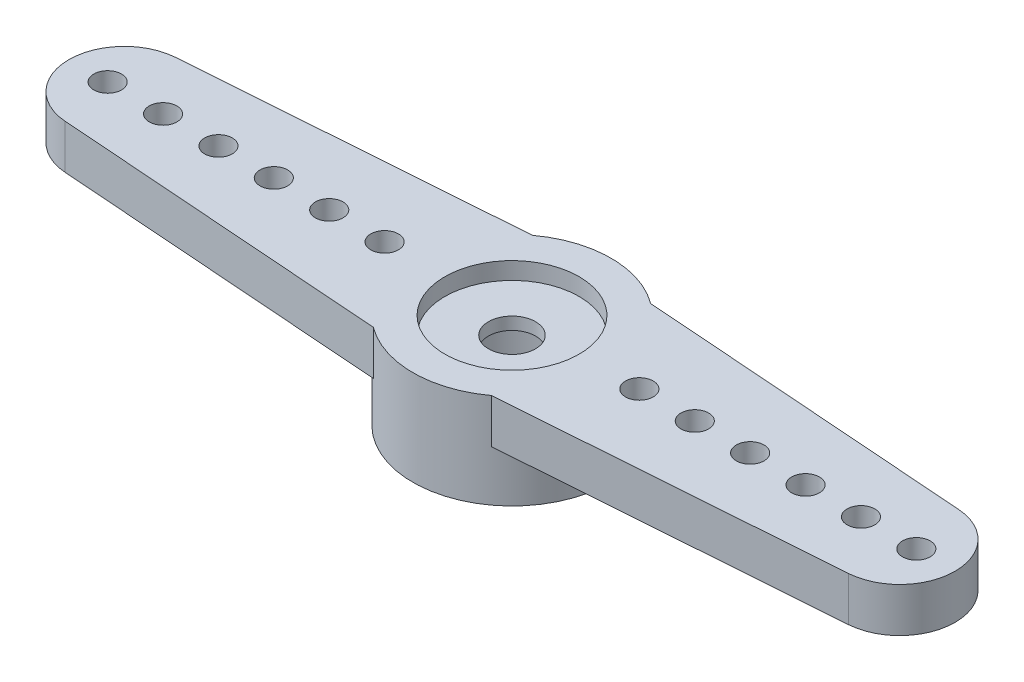
SolidWorks part; units mm, degrees
ref_plane "Alzado" through (0, 0, 0) normal (0, 0, 1) x (1, 0, 0)
ref_plane "Planta" through (0, 0, 0) normal (0, 1, 0) x (1, 0, 0)
ref_plane "Vista lateral" through (0, 0, 0) normal (1, 0, 0) x (0, 0, -1)
ref_plane "Plano1" through (0, 14.27, 0) normal (0, 1, 0) x (1, 0, 0)
sketch "Croquis1" plane through (0, 14.27, 0) normal (0, 1, 0) x (1, 0, 0)
  line L0 (8.0333, 3.025) -> (20.0462, 3.9053)
  line L1 (20.0462, 7.8947) -> (8.0333, 8.775)
  line L2 (3.7667, 8.775) -> (-8.2462, 7.8947)
  line L3 (-8.2462, 3.9053) -> (3.7667, 3.025)
  arc A0 (3.7667, 3.025) -> (8.0333, 3.025) centre (5.9, 5.9) ccw
  arc A1 (20.0462, 3.9053) -> (20.0462, 7.8947) centre (19.9, 5.9) ccw
  arc A2 (8.0333, 8.775) -> (3.7667, 8.775) centre (5.9, 5.9) ccw
  arc A3 (-8.2462, 7.8947) -> (-8.2462, 3.9053) centre (-8.1, 5.9) ccw
extrude "Saliente-Extruir1" add sketch "Croquis1" against normal blind 1.6
sketch "Croquis2" plane through (0, 12.67, 0) normal (0, -1, 0) x (1, 0, 0)
  circle A0 centre (5.9, -5.9) radius 3.58
extrude "Saliente-Extruir2" add sketch "Croquis2" along normal blind 1.83
ref_plane "Plano2" through (0, 0, -5.9) normal (0, 0, 1) x (1, 0, 0)
sketch "Croquis3" plane through (0, 0, -5.9) normal (0, 0, 1) x (1, 0, 0)
  line L0 (8.325, 14.27) -> (5.9, 14.27)
  line L1 (5.9, 14.27) -> (5.9, 10.84)
  line L2 (5.9, 10.84) -> (8.2, 10.84)
  line L3 (8.2, 10.84) -> (8.2, 13.2)
  line L4 (8.2, 13.2) -> (6.75, 13.2)
  line L5 (6.75, 13.2) -> (6.75, 13.65)
  line L6 (6.75, 13.65) -> (8.325, 13.65)
  line L7 (8.325, 13.65) -> (8.325, 14.27)
  line L8 (5.9, 14.27) -> (5.9, 10.84) construction
revolve "Cortar-Revolución1" cut sketch "Croquis3" angle 360 about L8 reverse direction yes
hole_wizard "Diámetro de taladro Ø1.0 (1)1" positions "Croquis5" profile "Croquis4" hole size "Ø1.0" standard "Ansi Metric"
sketch "Croquis5" plane through (0, 12.67, 0) normal (0, -1, 0) x (-1, 0, 0)
  point P0 (2.7, 5.9)
  point P1 (6.7, 5.9)
  point P2 (8.7, 5.9)
  point P3 (4.7, 5.9)
  point P4 (0.7, 5.9)
  point P5 (-10.5, 5.9)
  point P6 (-14.5, 5.9)
  point P7 (-18.5, 5.9)
  point P8 (-20.5, 5.9)
  point P9 (-16.5, 5.9)
  point P10 (-12.5, 5.9)
  point P11 (-1.3, 5.9)
sketch "Croquis4" plane through (-2.7, 12.67, -5.9) normal (1, 0, 0) x (0, 0, -1)
  line L0 (0, 0) -> (0, 1.6)
  line L1 (0, 1.6) -> (0.5, 1.6)
  line L2 (0.5, 1.6) -> (0.5, 0)
  line L5 (0.5, 0) -> (0, 0)
  line L11 (0, -6.35) -> (0, 107.95) construction
  dimension "Diámetro de taladro hasta el siguiente" = 1
  dimension "Profundidad de taladro hasta el siguiente" = 1.6
ref_axis "Eje1" through (5.9, 13.2, -5.9) along (0, -1, 0)
